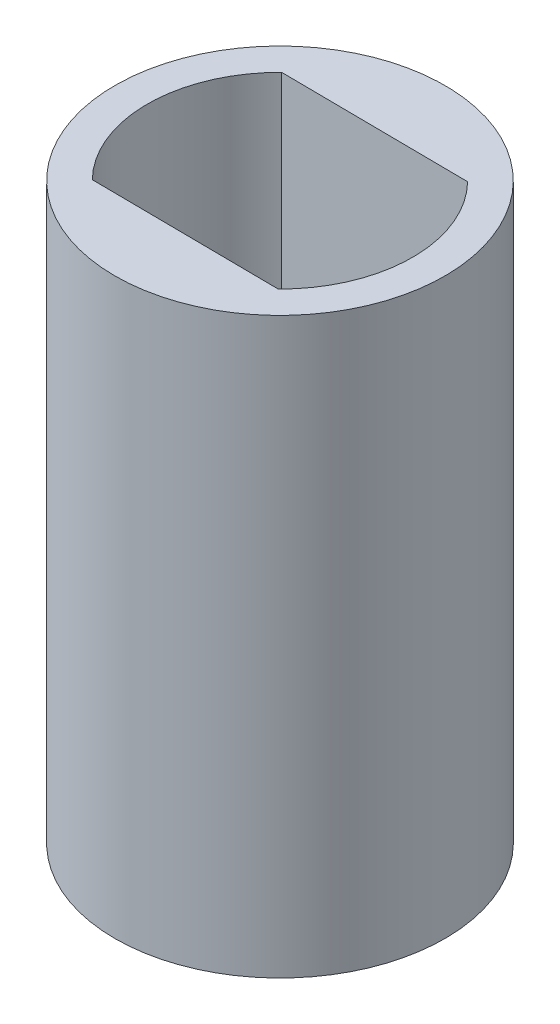
SolidWorks part; units mm, degrees
note: The reader was unsure of these and kept them because the rebuilt part matched: shared geometry of "Sketch3<3>".
ref_plane "Front Plane" through (0, 0, 0) normal (0, 0, 1) x (1, 0, 0)
ref_plane "Top Plane" through (0, 0, 0) normal (0, 1, 0) x (1, 0, 0)
ref_plane "Right Plane" through (0, 0, 0) normal (1, 0, 0) x (0, 0, -1)
sketch "Sketch1" plane through (0, 0, 0) normal (0, 1, 0) x (1, 0, 0)
  circle A0 centre (0, 0) radius 3.45
  dimension "D1" = 6.9
  dimension "D2" = 0
extrude "Boss-Extrude1" add sketch "Sketch1" along normal blind 12
sketch "Sketch2" plane through (0, 12, 0) normal (0, 1, 0) x (1, 0, 0)
  line L0 (0, 0) -> (1.9805, 1.9437) construction
  line L1 (1.9437, -1.9805) -> (-1.9805, -1.9437)
  line L2 (1.9805, 1.9437) -> (-1.9437, 1.9805)
  line L3 (0, 0) -> (1.9437, -1.9805) construction
  circle A0 centre (0, 0) radius 2.775
  dimension "D1" = 5.55
  dimension "D6" = 0
  dimension "D2" = 0
  dimension "D3" = 0
  dimension "D4" = 90
  dimension "D5" = 2.775
  dimension "D7" = 0
  dimension "D8" = 0
  dimension "D9" = 45
  dimension "D10" = 45
  dimension "D11" = 3.9243
  dimension "D12" = 1.9622
  dimension "D13" = 2.775
  dimension "D14" = 1.9622
extrude "Cut-Extrude1" cut sketch "Sketch2" against normal blind 6
sketch "Sketch3" plane through (0, 0, 0) normal (0, -1, 0) x (1, 0, 0)
  line L1 (-0.95, -2.44) -> (0.95, -2.44)
  line L2 (-0.95, -2.44) -> (-0.95, 2.44)
  line L3 (-0.95, 2.44) -> (0.95, 2.44)
  line L4 (0.95, -2.44) -> (0.95, 2.44)
  line L5 (-2.44, 0.95) -> (2.44, 0.95)
  line L6 (-2.44, 0.95) -> (-2.44, -0.95)
  line L7 (-2.44, -0.95) -> (2.44, -0.95)
  line L8 (2.44, 0.95) -> (2.44, -0.95)
  dimension "D1" = 0.95
  dimension "D2" = 0.95
  dimension "D3" = 2.44
  dimension "D4" = 2.44
  dimension "D5" = 0.95
  dimension "D6" = 0.95
  dimension "D7" = 2.44
  dimension "D8" = 2.44
extrude "Cut-Extrude3" cut sketch "Sketch3<3>" against normal blind 6 contours L2 L7 L4 L5 | L6 L7 L2 L5 | L8 L5 L4 L7 | L7 L2 L1 L4 | L2 L5 L4 L3
sketch "Sketch3<3>" plane through (0, 0, 0) normal (0, -1, 0) x (1, 0, 0) same geometry as "Sketch3"
extrude "Cut-Extrude2" cut sketch "Sketch3" against normal blind 6 contours L2 L7 L4 L5 | L6 L7 L2 L5 | L7 L2 L1 L4 | L8 L5 L4 L7 | L2 L5 L4 L3
